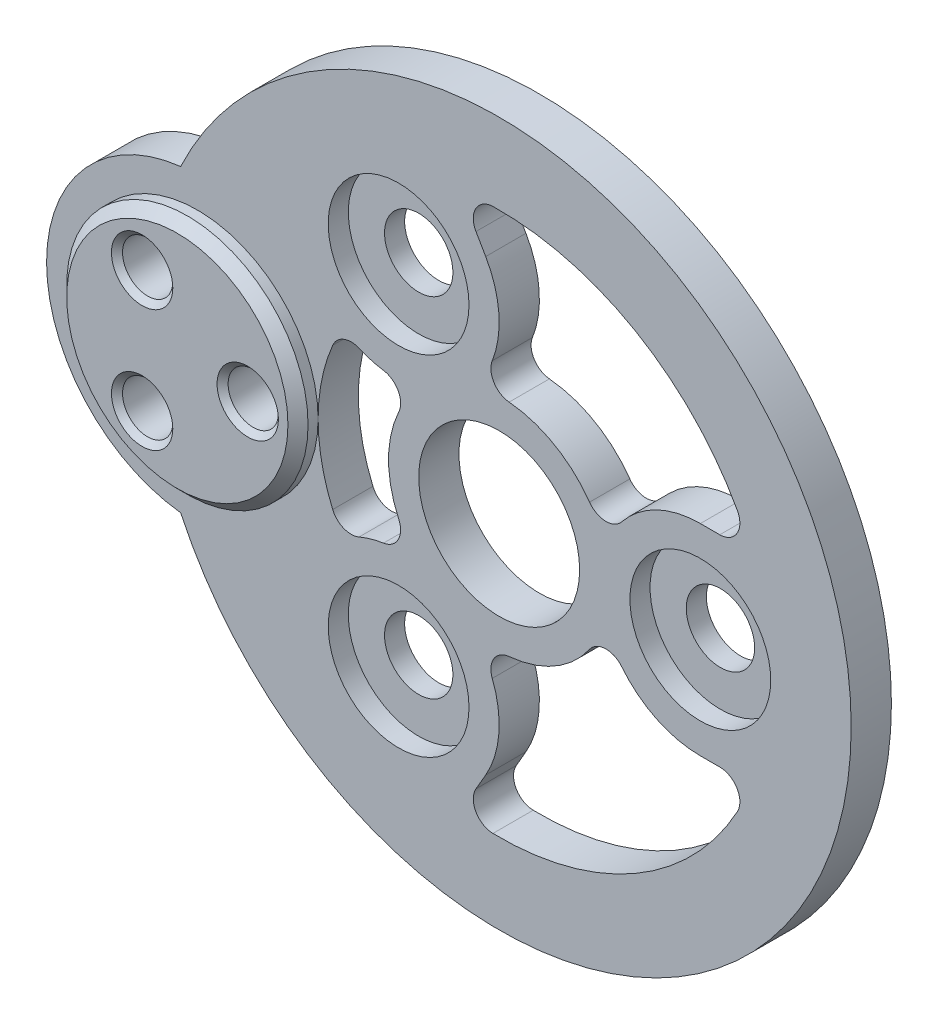
SolidWorks part; units mm, degrees
material "A2017"
ref_plane "正面" through (0, 0, 0) normal (0, 0, 1) x (1, 0, 0)
ref_plane "平面" through (0, 0, 0) normal (0, 1, 0) x (1, 0, 0)
ref_plane "右側面" through (0, 0, 0) normal (1, 0, 0) x (0, 0, -1)
sketch "ｽｹｯﾁ1" plane through (0, 0, 0) normal (0, 0, 1) x (1, 0, 0)
  line L0 (-15, 0) -> (0, 0) construction
  circle A0 centre (0, 0) radius 4
  arc A1 (-4.5, -6) -> (-4.5, 6) centre (0, 0) ccw
  arc A2 (-10.5, 6) -> (-10.5, -6) centre (-15, 0) ccw
  arc A3 (-10.5, 6) -> (-4.5, 6) centre (-7.5, 10) ccw
  arc A4 (-10.5, -6) -> (-4.5, -6) centre (-7.5, -10) cw
  dimension "D1" = 8
  dimension "D2" = 15
  dimension "D3" = 15
  dimension "D4" = 5
extrude "ﾎﾞｽ - 押し出し1" add sketch "ｽｹｯﾁ1" along normal blind 2
sketch "ｽｹｯﾁ6" plane through (0, 0, 2) normal (0, 0, 1) x (1, 0, 0)
  circle A0 centre (-15, 0) radius 6
  dimension "D1" = 12
extrude "ﾎﾞｽ - 押し出し3" add sketch "ｽｹｯﾁ6" along normal blind 1
sketch "ｽｹｯﾁ2" plane through (0, 0, 3) normal (0, 0, 1) x (1, 0, 0)
  circle A0 centre (-15, 0) radius 5 construction
  circle A1 centre (-11.5, 0) radius 1.5 construction
  circle A2 centre (-11.5, 0) radius 0.5
  dimension "D1" = 10
  dimension "D2" = 3
  dimension "D3" = 1
extrude "ｶｯﾄ - 押し出し1" cut sketch "ｽｹｯﾁ2" against normal blind 2
hole_wizard "M3x0.5 ねじ穴1" positions "ｽｹｯﾁ3" profile "ｽｹｯﾁ4" tap size "M3x0.5" standard "JIS" end condition through all
sketch "ｽｹｯﾁ3" plane through (0, 0, 3) normal (0, 0, 1) x (1, 0, 0)
  point P0 (-11.5, 0)
sketch "ｽｹｯﾁ4" plane through (-11.5, 0, 3) normal (1, 0, 0) x (0, -1, 0)
  line L0 (0, 0) -> (0, 3)
  line L1 (0, 3) -> (1.525, 3)
  line L2 (1.25, 2.725) -> (1.25, 0.275)
  line L3 (1.25, 0.275) -> (1.525, 0)
  line L5 (1.525, 0) -> (0, 0)
  line L6 (-1.25, 0.275) -> (-1.525, 0) construction
  line L7 (1.525, 3) -> (1.25, 2.725)
  line L8 (-1.525, 3) -> (-1.25, 2.725) construction
  line L11 (0, -6.35) -> (0, 107.95) construction
  dimension "次ｻｰﾌｪｽまでのねじ下穴ﾄﾞﾘﾙ直径" = 2.5
  dimension "次ｻｰﾌｪｽまでのねじ下穴ﾄﾞﾘﾙの深さ" = 3
  dimension "表面の皿穴の直径" = 3.05
  dimension "表面の皿穴の角度" = 90
  dimension "裏面の皿穴の直径" = 3.05
  dimension "裏面の皿穴の角度" = 90
cosmetic thread "穴のねじ山1" parameters "D2"=3
pattern_circular "円形ﾊﾟﾀｰﾝ1" count 3 over 360 about axis through (-15, 0, 2) along (0, 0, -1) of "M3x0.5 ねじ穴1"
chamfer "面取り1" distance 0.5 angle 45 1 edges at (-9, 0, 3)
chamfer "面取り2" [suppressed] distance 0.5 angle 45
chamfer "面取り3" [suppressed] distance 0.1 angle 45
sketch "ｽｹｯﾁ7" plane through (0, 0, 2) normal (0, 0, 1) x (1, 0, 0)
  circle A0 centre (0, 0) radius 17.5
  arc A5 (-10.5, 6) -> (-4.5, 6) centre (-7.5, 10) ccw
  arc A6 (-10.5, 6) -> (-10.5, -6) centre (-15, 0) ccw
  arc A7 (-4.5, -6) -> (-10.5, -6) centre (-7.5, -10) ccw
  arc A8 (-4.5, -6) -> (-4.5, 6) centre (0, 0) ccw
  arc A9 (-10.5, 6) -> (-4.5, 6) centre (-7.5, 10) ccw
  arc A10 (-10.5, 6) -> (-10.5, -6) centre (-15, 0) ccw
  arc A11 (-4.5, -6) -> (-10.5, -6) centre (-7.5, -10) ccw
  arc A12 (-4.5, -6) -> (-4.5, 6) centre (0, 0) ccw
  point P3 (0, -0.2142)
  circle M5 centre (-15, 0) radius 6
  arc M6 (-4.5, 6) -> (-10.5, 6) centre (-7.5, 10) cw
  arc M7 (-10.5, 6) -> (-10.5, -6) centre (-15, 0) ccw
  arc M8 (-10.5, -6) -> (-4.5, -6) centre (-7.5, -10) cw
  arc M9 (-4.5, -6) -> (-4.5, 6) centre (0, 0) ccw
  circle M10 centre (0, 0) radius 4
  dimension "D1" = 35
  dimension "D2" = 0
extrude "ﾎﾞｽ - 押し出し4" add sketch "ｽｹｯﾁ7" against normal up to surface (2 mm away) contours A0 M7 M6 M9 M8 | A0 M7 M5 M8 M9 M6 M10 region at (3.7133, -16.6066, 2) region at (-13.1023, 6.9629, 2) up to face at (-17.5125, 4.3518, 0)
hole_wizard "M3 すきま穴1" positions "ｽｹｯﾁ9" profile "ｽｹｯﾁ10" hole size "M3" standard "JIS" end condition through all
sketch "ｽｹｯﾁ9" plane through (0, 0, 2) normal (0, 0, 1) x (1, 0, 0)
  point P0 (-5, 8.6603)
  point P3 (-5, -8.6603)
  point P6 (10, 0)
sketch "ｽｹｯﾁ10" plane through (-5, 8.6603, 2) normal (1, 0, 0) x (0, -1, 0)
  line L0 (0, 0) -> (0, 2)
  line L1 (0, 2) -> (1.7, 2)
  line L2 (1.7, 2) -> (1.7, 0)
  line L5 (1.7, 0) -> (0, 0)
  line L11 (0, -6.35) -> (0, 107.95) construction
  dimension "通し穴の直径" = 3.4
  dimension "通し穴の深さ" = 2
sketch "ｽｹｯﾁ11" plane through (0, 0, 2) normal (0, 0, 1) x (1, 0, 0)
  circle A0 centre (-5, 8.6603) radius 3.5
  circle A1 centre (10, 0) radius 3.5
  circle A2 centre (-5, -8.6603) radius 3.5
  point P3 (10, 0)
  point P11 (0, 0)
  dimension "D1" = 7
  dimension "D2" = 3
extrude "ｶｯﾄ - 押し出し3" cut sketch "ｽｹｯﾁ11" against normal blind 1
sketch "ｽｹｯﾁ12" plane through (0, 0, 2) normal (0, 0, 1) x (1, 0, 0)
  line L0 (10, 0) -> (13.5, 0) construction
  line L1 (10, 5) -> (13.5, 5)
  line L2 (10, -5) -> (13.5, -5)
  line L3 (-5, -8.6603) -> (-6.75, -11.6913) construction
  line L4 (-0.6699, -11.1603) -> (-2.4199, -14.1913)
  line L5 (-9.3301, -6.1603) -> (-11.0801, -9.1913)
  line L6 (-5, 8.6603) -> (-6.75, 11.6913) construction
  line L7 (-9.3301, 6.1603) -> (-11.0801, 9.1913)
  line L8 (-0.6699, 11.1603) -> (-2.4199, 14.1913)
  circle A0 centre (0, 0) radius 13.5
  circle A1 centre (0, 0) radius 5.5
  arc A2 (10, 5) -> (10, -5) centre (10, 0) ccw
  arc A3 (13.5, -5) -> (13.5, 5) centre (13.5, 0) ccw
  arc A4 (-0.6699, -11.1603) -> (-9.3301, -6.1603) centre (-5, -8.6603) ccw
  arc A5 (-11.0801, -9.1913) -> (-2.4199, -14.1913) centre (-6.75, -11.6913) ccw
  arc A6 (-9.3301, 6.1603) -> (-0.6699, 11.1603) centre (-5, 8.6603) ccw
  arc A7 (-2.4199, 14.1913) -> (-11.0801, 9.1913) centre (-6.75, 11.6913) ccw
  arc A8 (-0.3439, 6.8379) -> (0.4969, 5.4775) centre (0.5873, 6.4734) ccw
  arc A9 (4.4952, 3.1691) -> (6.0938, 3.1211) centre (5.3125, 3.7453) ccw
  arc A10 (0.4969, -5.4775) -> (-0.3439, -6.8379) centre (0.5873, -6.4734) ccw
  arc A11 (6.0938, -3.1211) -> (4.4952, -3.1691) centre (5.3125, -3.7453) ccw
  arc A12 (-4.9921, 2.3084) -> (-5.7498, 3.7168) centre (-5.8998, 2.7281) ccw
  arc A13 (-5.7498, -3.7168) -> (-4.9921, -2.3084) centre (-5.8998, -2.7281) ccw
  arc A14 (-7.7884, 4.51) -> (-7.7884, -4.51) centre (0, 0) ccw
  circle A15 centre (-15, 0) radius 6 construction
  point P7 (11.75, 0)
  point P16 (-5.875, -10.1758)
  point P23 (-5.875, 10.1758)
  point P28 (0, 0)
  point P48 (0, 0)
  dimension "D1" = 27
  dimension "D2" = 11
  dimension "D5" = 1
  dimension "D3" = 10
  dimension "D4" = 3
  dimension "D6" = 3
extrude "ｶｯﾄ - 押し出し4" cut sketch "ｽｹｯﾁ12" against normal through all contours A1 A9 A2 L1 A0 L8 A6 A8 | A2 A11 A1 A10 A4 L4 A0 L2 | A6 A14 A4 A13 A1 A12 region at (4.8059, 8.3241, 2) region at (4.8059, -8.3241, 2) region at (-7.0052, 0, 2)
fillet "ﾌｨﾚｯﾄ1" radius 1 6 edges at (12.5399, -5, 1) (-1.9398, -13.3599, 1) (12.5399, 5, 1) (-7.7884, -4.51, 1) (-7.7884, 4.51, 1) (-1.9398, 13.3599, 1)
